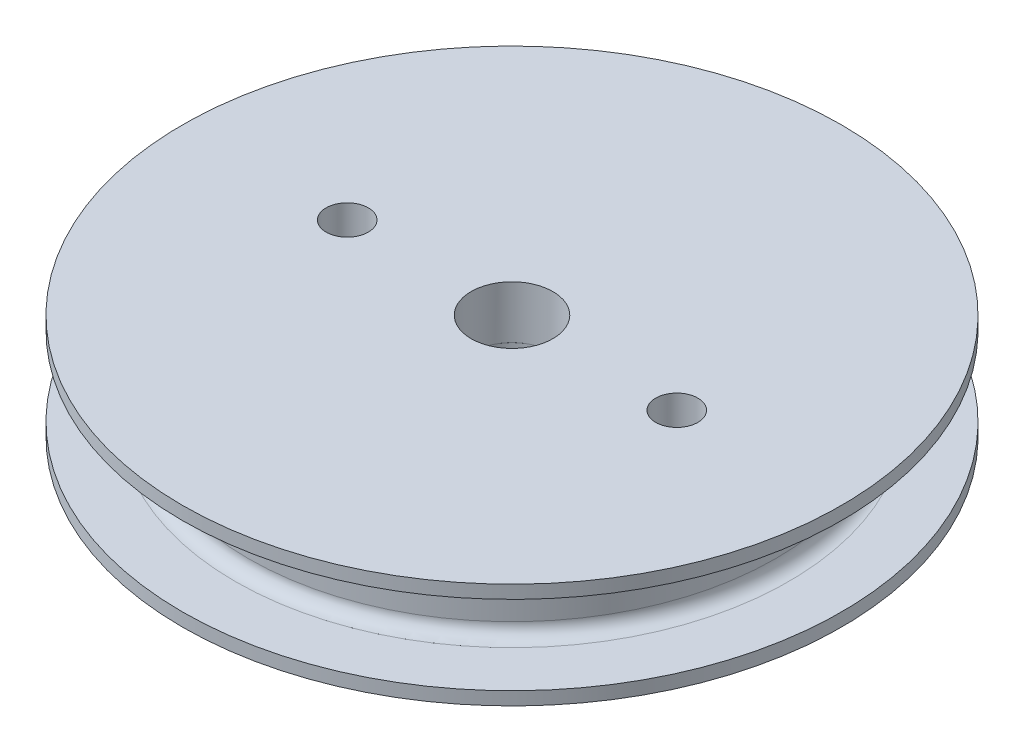
SolidWorks part; units mm, degrees
material "ﾊﾞﾙｻ"
ref_plane "正面" through (0, 0, 0) normal (0, 0, 1) x (1, 0, 0)
ref_plane "平面" through (0, 0, 0) normal (0, 1, 0) x (1, 0, 0)
ref_plane "右側面" through (0, 0, 0) normal (1, 0, 0) x (0, 0, -1)
sketch "ｽｹｯﾁ1" plane through (0, 0, 0) normal (0, 0, 1) x (1, 0, 0)
  line L0 (0, 0) -> (0, 4)
  line L1 (0, 4) -> (20, 4)
  line L3 (25, 0) -> (0, 0)
  line L5 (20, 4) -> (20, 2)
  line L6 (21, 1) -> (25, 1)
  line L7 (25, 1) -> (25, 0)
  arc A1 (20, 2) -> (21, 1) centre (21, 2) ccw
  point P11 (20, 1)
  dimension "D5" = 1
  dimension "D1" = 3
  dimension "D2" = 5
  dimension "D3" = 20
  dimension "D4" = 1
revolve "回転1" add sketch "ｽｹｯﾁ1" angle 360 about L0
mirror "ﾐﾗｰ1" about plane through (0, 4, 0) normal (0, 1, 0) of bodies 101
sketch "ｽｹｯﾁ2" plane through (0, 8, 0) normal (0, 1, 0) x (1, 0, 0)
  circle A0 centre (0, 0) radius 3.1
  dimension "D1" = 6.2
extrude "ｶｯﾄ - 押し出し1" cut sketch "ｽｹｯﾁ2" against normal through all
sketch "ｽｹｯﾁ3" plane through (0, 0, 0) normal (0, -1, 0) x (1, 0, 0)
  line L0 (0, 0) -> (12.5, 0) construction
  line L1 (-12.5, 0) -> (0, 0) construction
  circle A0 centre (12.5, 0) radius 1.6
  circle A1 centre (-12.5, 0) radius 1.6
  point P8 (0, 0)
  dimension "D1" = 3.2
  dimension "D3" = 25
  dimension "D2" = 2
extrude "ｶｯﾄ - 押し出し2" cut sketch "ｽｹｯﾁ3" against normal through all
